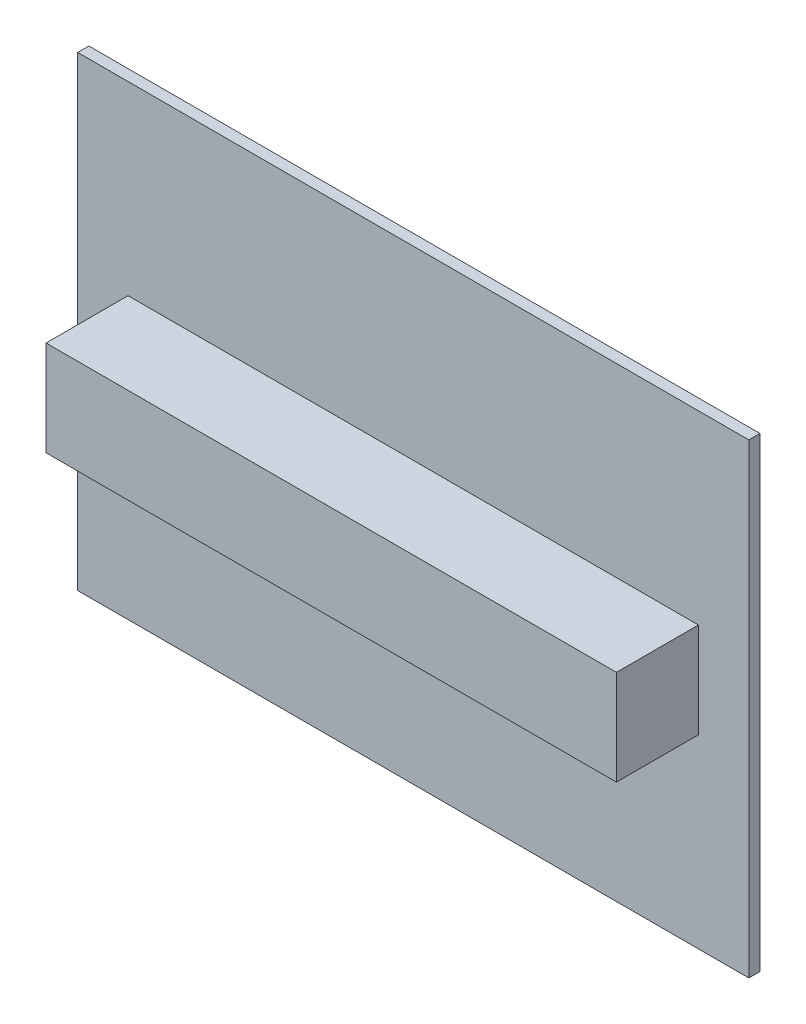
SolidWorks part; units mm, degrees
ref_plane "前视基准面" through (0, 0, 0) normal (0, 0, 1) x (1, 0, 0)
ref_plane "上视基准面" through (0, 0, 0) normal (0, 1, 0) x (1, 0, 0)
ref_plane "右视基准面" through (0, 0, 0) normal (1, 0, 0) x (0, 0, -1)
sketch "草图1" plane through (0, 0, 0) normal (0, 0, 1) x (1, 0, 0)
  line L1 (-90, 62.5) -> (90, 62.5)
  line L2 (-90, 62.5) -> (-90, -62.5)
  line L3 (-90, -62.5) -> (90, -62.5)
  line L4 (90, 62.5) -> (90, -62.5)
  line L5 (-90, 62.5) -> (90, -62.5) construction
  line L6 (-90, -62.5) -> (90, 62.5) construction
  point P0 (0, 0)
  dimension "D1" = 125
  dimension "D2" = 180
extrude "凸台-拉伸1" add sketch "草图1" along normal blind 3
sketch "草图7" plane through (0, 0, 0) normal (0, 0, -1) x (-1, 0, 0)
  line L1 (-74, 10.25) -> (74, 10.25)
  line L2 (-74, 10.25) -> (-74, -10.25)
  line L3 (-74, -10.25) -> (74, -10.25)
  line L4 (74, 10.25) -> (74, -10.25)
  line L5 (0, 0) -> (72.729, 0) construction
  line L8 (0, 0) -> (0, -50.9103) construction
  dimension "D1" = 20.5
  dimension "D2" = 148
extrude "电池位切除-拉伸3" cut sketch "草图7" against normal up to next
sketch "草图8" plane through (0, 0, 3) normal (0, 0, 1) x (1, 0, 0)
  line L12 (74, 10.25) -> (74, -10.25) construction
  line L13 (-76.5, 12.75) -> (76.5, 12.75)
  line L14 (-76.5, 12.75) -> (-76.5, -12.75)
  line L15 (-76.5, -12.75) -> (76.5, -12.75)
  line L16 (76.5, 12.75) -> (76.5, -12.75)
  line L17 (-74, -10.25) -> (-74, 10.25) construction
  line L18 (-74, 10.25) -> (74, 10.25) construction
  line L19 (74, -10.25) -> (-74, -10.25) construction
  line L20 (-74, 10.25) -> (74, 10.25)
  line L21 (74, -10.25) -> (-74, -10.25)
  line L22 (74, 10.25) -> (74, -10.25)
  line L23 (-74, -10.25) -> (-74, 10.25) construction
  line L24 (-74, -10.25) -> (-74, 10.25)
  dimension "D1" = 2.5
  dimension "D2" = 2.5
  dimension "D3" = 2.5
  dimension "D4" = 2.5
extrude "凸台-拉伸2" add sketch "草图8" along normal blind 22
sketch "草图9" plane through (0, 0, 25) normal (0, 0, 1) x (1, 0, 0)
  line L0 (76.5, 12.75) -> (-76.5, 12.75) construction
  line L5 (76.5, 12.75) -> (-76.5, 12.75)
  line L6 (-76.5, -12.75) -> (76.5, -12.75) construction
  line L7 (-76.5, -12.75) -> (76.5, -12.75)
  line L8 (76.5, -12.75) -> (76.5, 12.75) construction
  line L9 (76.5, -12.75) -> (76.5, 12.75)
  line L10 (-76.5, 12.75) -> (-76.5, -12.75) construction
  line L11 (-76.5, 12.75) -> (-76.5, -12.75)
extrude "凸台-拉伸3" add sketch "草图9" against normal blind 2.5
sketch "草图4" plane through (0, 0, 0) normal (0, 0, -1) x (-1, 0, 0)
  line L0 (74, -10.25) -> (74, 10.25) construction
  line L5 (74, 0) -> (84.6307, 0) construction
  line L10 (83.2374, -53.4277) -> (79.3374, -53.4277) construction
  line L11 (83.2374, -49.6277) -> (83.2374, -53.4277) construction
  line L12 (79.3374, -49.6277) -> (83.2374, -49.6277) construction
  line L29 (74, -4) -> (78, -4)
  line L30 (78, -4) -> (78, 4)
  line L31 (78, 4) -> (74, 4)
  line L32 (74, 4) -> (74, -4)
  dimension "D1" = 8
  dimension "D2" = 4
extrude "切除-拉伸2" cut sketch "草图4" along normal blind 1.6 from surface starting at face at (0, 0, 3)
